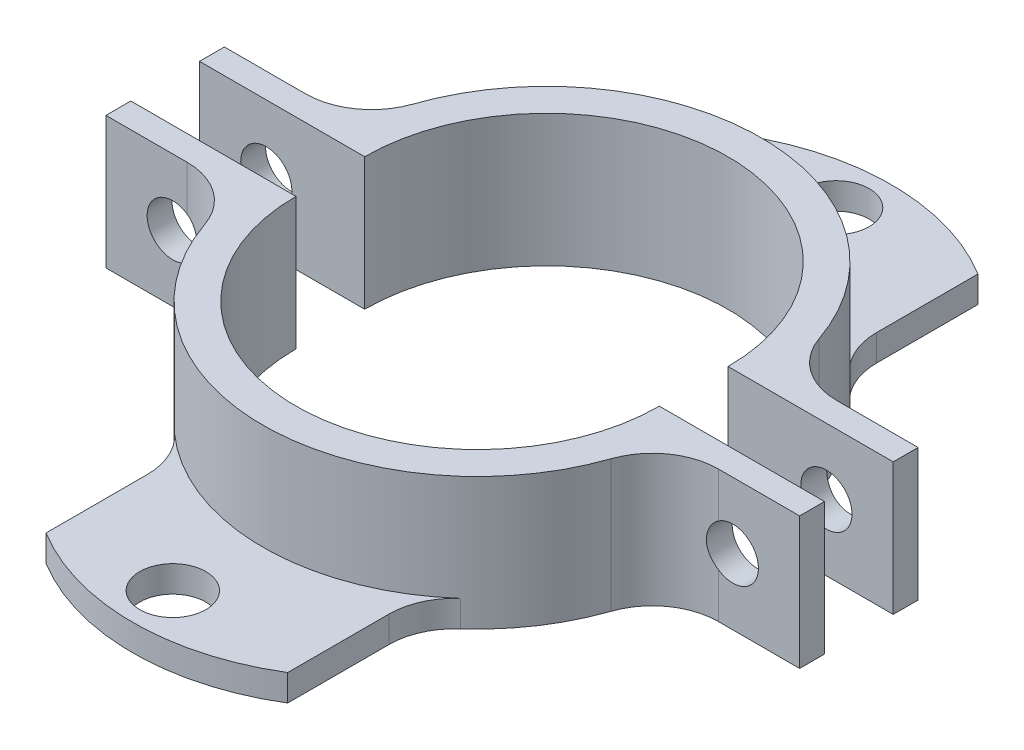
SolidWorks part; units mm, degrees
material "6061 Alloy"
ref_plane "Front Plane" through (0, 0, 0) normal (0, 0, 1) x (1, 0, 0)
ref_plane "Top Plane" through (0, 0, 0) normal (0, 1, 0) x (1, 0, 0)
ref_plane "Right Plane" through (0, 0, 0) normal (1, 0, 0) x (0, 0, -1)
sketch "Sketch1" plane through (0, 0, 0) normal (0, 1, 0) x (1, 0, 0)
  line L0 (-20.6375, 0) -> (-17.4625, 0)
  line L1 (17.4625, 0) -> (20.6375, 0)
  line L2 (20.6375, 0) -> (33.3375, 0)
  line L3 (33.3375, 0) -> (33.3375, 2.3916)
  line L4 (-11.6154, 29.8712) -> (-11.6154, 17.0584)
  line L5 (11.6154, 29.8712) -> (11.6154, 17.0584)
  line L6 (33.3375, 2.3916) -> (20.4985, 2.3916)
  line L7 (33.3375, 0) -> (20.6375, 0)
  line L8 (0, 0) -> (0, -13.251) construction
  line L9 (-20.6375, 0) -> (-33.3375, 0)
  line L10 (-33.3375, 0) -> (-33.3375, 2.3916)
  line L11 (-33.3375, 2.3916) -> (-20.4985, 2.3916)
  arc A0 (20.6375, 0) -> (-20.6375, 0) centre (0, 0) ccw
  arc A1 (17.4625, 0) -> (-17.4625, 0) centre (0, 0) ccw
  arc A2 (11.6154, 29.8712) -> (-11.6154, 29.8712) centre (0, 10.923) ccw
  circle A3 centre (-0.7251, 28.575) radius 3.175
  dimension "D1" = 28.575
  dimension "D2" = 3.175
  dimension "D3" = 12.7
  dimension "D5" = 6.35
  dimension "D4" = 2.3916
extrude "Boss-Extrude3" add sketch "Sketch1" along normal blind 12.7 contours A1 L1 A0 L0 | A0 L2 L3 L6 | A0 L11 L10 L9 region at (-20.142, 0, -1.171) region at (-26.9643, 0, -1.198) region at (26.9643, 0, -1.198)
extrude "Boss-Extrude4" add sketch "Sketch1<8>" along normal blind 2.54 contours L5 A2 L4 A0 A3 region at (0.088, 0, -25.444)
sketch "Sketch1<8>" plane through (0, 0, 0) normal (0, 1, 0) x (1, 0, 0) same geometry as "Sketch1"
hole_wizard "#10 (0.1935) Diameter Hole1" positions "Sketch4" profile "Sketch5" hole size "#10" standard "ANSI Inch" end condition up to next
sketch "Sketch4" plane through (0, 0, -2.3916) normal (0, 0, -1) x (-1, 0, 0)
  line L0 (-33.3375, 0) -> (-20.4985, 12.7) construction
  line L3 (20.4985, 12.7) -> (33.3375, 0) construction
  line L4 (33.3375, 0) -> (20.4985, 0) construction
  point P0 (-26.918, 6.35)
  point P2 (26.918, 6.35)
  point P23 (26.918, 6.35)
  point P25 (-26.918, 6.35)
sketch "Sketch5" plane through (26.918, 6.35, -2.3916) normal (1, 0, 0) x (0, 1, 0)
  line L0 (0, 0) -> (0, 2.3916)
  line L1 (0, 2.3916) -> (2.4574, 2.3916)
  line L2 (2.4574, 2.3916) -> (2.4574, 0)
  line L5 (2.4574, 0) -> (0, 0)
  line L11 (0, -6.35) -> (0, 107.95) construction
  dimension "Thru Hole Dia." = 4.9149
  dimension "Thru Hole Depth" = 2.3916
ref_plane "Plane1" through (0, 0, 3.302) normal (0, 0, 1) x (1, 0, 0)
fillet "Fillet1" radius 6.35 4 edges at (20.4985, 6.35, -2.3916) (11.6154, 1.27, -17.0584) (-11.6154, 1.27, -17.0584) (-20.4985, 6.35, -2.3916) tangent propagation no
mirror "Mirror3" about plane through (0, 0, 3.302) normal (0, 0, 1) of bodies 105
